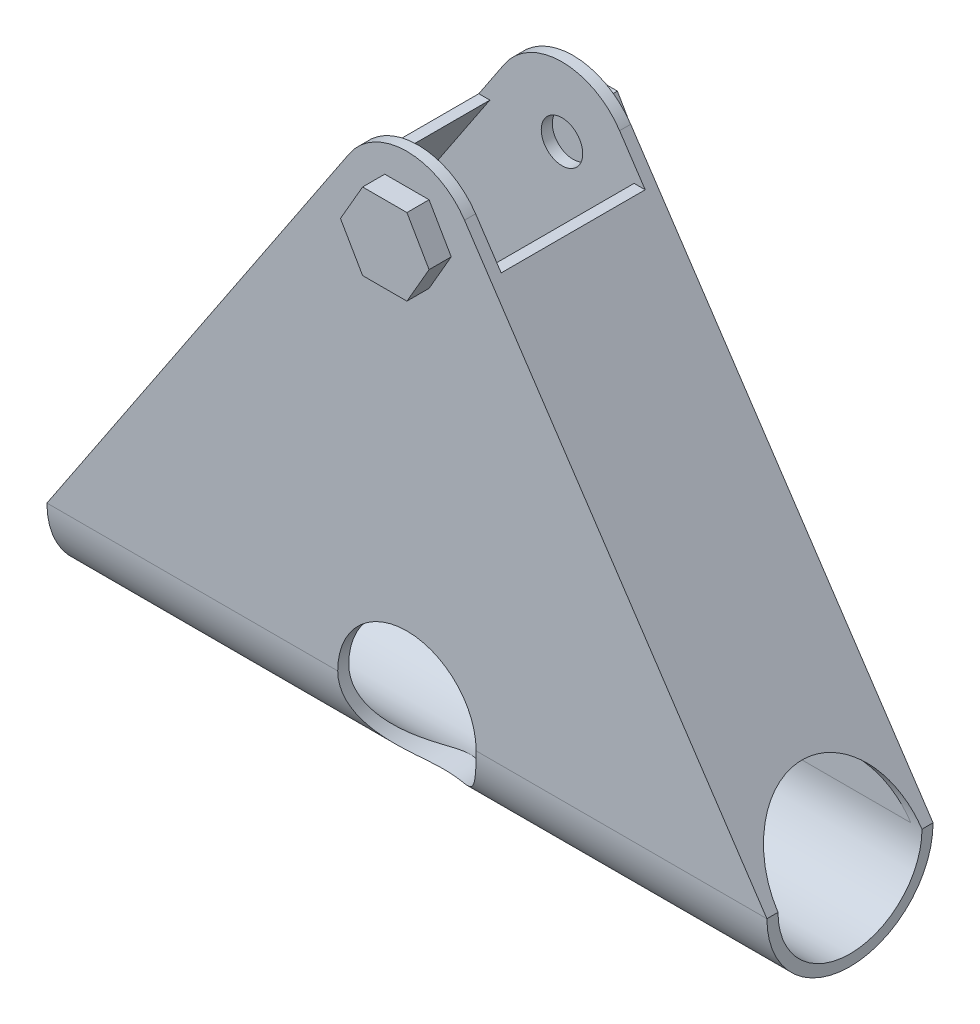
SolidWorks part; units mm, degrees
ref_plane "Front Plane" through (0, 0, 0) normal (0, 0, 1) x (1, 0, 0)
ref_plane "Top Plane" through (0, 0, 0) normal (0, 1, 0) x (1, 0, 0)
ref_plane "Right Plane" through (0, 0, 0) normal (1, 0, 0) x (0, 0, -1)
sketch "Sketch1" plane through (0, 0, 0) normal (0, 0, 1) x (1, 0, 0)
  line L0 (-10.402, 6.9317) -> (-65, -75)
  line L1 (-65, -75) -> (65, -75)
  line L2 (65, -75) -> (10.402, 6.9317)
  arc A0 (10.402, 6.9317) -> (-10.402, 6.9317) centre (0, 0) ccw
  circle A1 centre (0, 0) radius 3.75
  dimension "D4" = 25
  dimension "D5" = 7.5
  dimension "D1" = 75
  dimension "D2" = 65
  dimension "D3" = 130
extrude "Boss-Extrude1" add sketch "Sketch1" along normal blind 2
sketch "Sketch2" plane through (0, 0, 0) normal (1, 0, 0) x (0, 0, -1)
  line L0 (0, 0) -> (13, 0)
  line L5 (-2, -75) -> (0, -75)
  line L7 (26, -75) -> (28, -75)
  arc A0 (-2, -75) -> (28, -75) centre (13, -75) ccw
  arc A1 (0, -75) -> (26, -75) centre (13, -75) ccw
  dimension "D2" = 30
  dimension "D1" = 75
  dimension "D3" = 13
extrude "Boss-Extrude2" add sketch "Sketch2" along normal blind 65 and the other way blind 65 contours A1 A0 region at (0, -75.3354, 1)
sketch "Sketch3" plane through (0, 0, 0) normal (0, 1, 0) x (1, 0, 0)
  line L2 (-18.6982, 28) -> (18.6982, 28)
  point P8 (0, 28)
ref_plane "Plane1" through (0, 0, -28) normal (0, 0, -1) x (-1, 0, 0)
sketch "Sketch4" plane through (0, 0, -28) normal (0, 0, -1) x (-1, 0, 0)
  line L0 (-10.402, 6.9317) -> (-65, -75)
  line L1 (-65, -75) -> (65, -75)
  line L2 (65, -75) -> (10.402, 6.9317)
  circle A0 centre (0, 0) radius 3.75
  circle A1 centre (0, 0) radius 12.5
  dimension "D1" = 7.5
  dimension "D2" = 25
  dimension "D3" = 75
  dimension "D4" = 65
  dimension "D5" = 65
extrude "Boss-Extrude3" add sketch "Sketch4" against normal blind 2 contours A1 L0 L1 L2 | A1 A0 region at (0, -46.9089, -28) region at (0, 12.1464, -28)
sketch "Sketch5" plane through (0, 0, 0) normal (0, 0, 1) x (1, 0, 0)
  line L0 (-65, -75) -> (65, -75) construction
  circle A0 centre (0, -75) radius 12.5
  dimension "D1" = 25
extrude "Cut-Extrude1" cut sketch "Sketch5" against normal through all and the other way through all
sketch "Sketch6" plane through (0, 0, 0) normal (0, 0, 1) x (1, 0, 0)
  line L0 (15.0212, 0) -> (13.0212, 0)
  line L1 (65, -75) -> (10.402, 6.9317) construction
  line L2 (13.0212, 0) -> (63, -75)
  line L3 (63, -75) -> (65, -75)
  line L4 (65, -75) -> (15.0212, 0)
  line L5 (-13.0212, 0) -> (-15.0212, 0)
  line L6 (-10.402, 6.9317) -> (-65, -75) construction
  line L7 (-15.0212, 0) -> (-65, -75)
  line L8 (-65, -75) -> (-63, -75)
  line L9 (-63, -75) -> (-13.0212, 0)
  dimension "D1" = 2
  dimension "D2" = 2
  dimension "D3" = 2
  dimension "D4" = 2
extrude "Boss-Extrude4" add sketch "Sketch6" against normal blind 26
sketch "Sketch7" plane through (0, 0, 0) normal (1, 0, 0) x (0, 0, -1)
  line L0 (26, -75) -> (0, -75) construction
  circle A0 centre (13, -75) radius 13
extrude "Cut-Extrude2" cut sketch "Sketch7" against normal through all and the other way through all
sketch "Sketch8" plane through (0, 0, -28) normal (0, 0, -1) x (-1, 0, 0)
  line L1 (8, 0) -> (4, 6.9282)
  line L2 (4, 6.9282) -> (-4, 6.9282)
  line L3 (-4, 6.9282) -> (-8, 0)
  line L4 (-8, 0) -> (-4, -6.9282)
  line L5 (-4, -6.9282) -> (4, -6.9282)
  line L6 (4, -6.9282) -> (8, 0)
  circle A0 centre (0, 0) radius 6.9282 construction
  dimension "D1" = 8
extrude "Boss-Extrude5" add sketch "Sketch8" along normal blind 4
sketch "Sketch9" plane through (0, 0, 2) normal (0, 0, 1) x (1, 0, 0)
  line L1 (8, 0) -> (4, 6.9282)
  line L2 (4, 6.9282) -> (-4, 6.9282)
  line L3 (-4, 6.9282) -> (-8, 0)
  line L4 (-8, 0) -> (-4, -6.9282)
  line L5 (-4, -6.9282) -> (4, -6.9282)
  line L6 (4, -6.9282) -> (8, 0)
  circle A0 centre (0, 0) radius 6.9282 construction
  dimension "D1" = 16
extrude "Boss-Extrude6" add sketch "Sketch9" along normal blind 4
